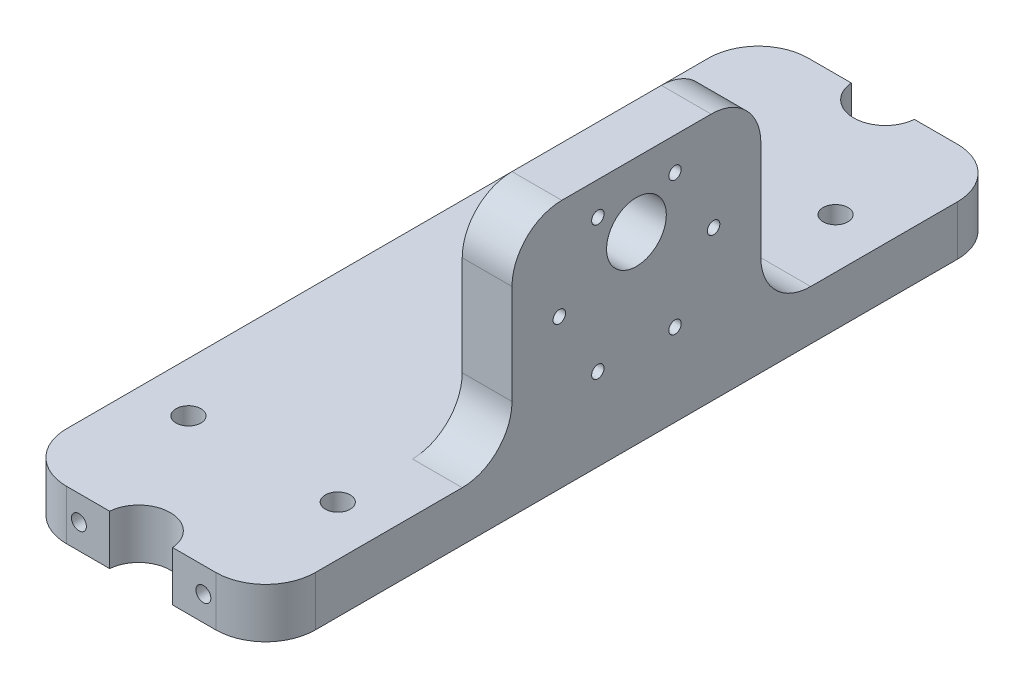
SolidWorks part; units mm, degrees
material "Nylon 101"
ref_plane "Front" through (0, 0, 0) normal (0, 0, 1) x (1, 0, 0)
ref_plane "Top" through (0, 0, 0) normal (0, 1, 0) x (1, 0, 0)
ref_plane "Right" through (0, 0, 0) normal (1, 0, 0) x (0, 0, -1)
sketch "Sketch1" plane through (0, 0, 0) normal (0, 1, 0) x (1, 0, 0)
  line L0 (-25, -75) -> (25, -75) construction
  line L1 (-15, 50) -> (15, 50) construction
  line L2 (0, -75) -> (0, 75) construction
  line L3 (-25, -75) -> (-25, 75)
  line L4 (25, -75) -> (25, 75)
  line L5 (25, 0) -> (0, 0) construction
  line L6 (25, 17) -> (97.2, 17)
  line L7 (25, 17) -> (25, -17)
  line L8 (25, -17) -> (97.2, -17)
  line L9 (97.2, 17) -> (97.2, -17)
  line L10 (-15, 50) -> (-15, -50) construction
  line L11 (-15, -50) -> (15, -50) construction
  line L12 (15, 50) -> (15, -50) construction
  line L13 (-25, -75.5) -> (25, -75.5)
  line L14 (-25, -74.5) -> (25, -74.5)
  line L15 (-25, 75.5) -> (25, 75.5)
  line L16 (-25, 74.5) -> (25, 74.5)
  circle A0 centre (0, 75) radius 6.35
  circle A1 centre (0, -75) radius 6.35
  arc A2 (-25, -75) -> (25, -75) centre (0, -75) ccw
  arc A3 (25, 75) -> (-25, 75) centre (0, 75) ccw
  circle A6 centre (-15, 50) radius 2.5
  circle A7 centre (-15, -50) radius 2.5
  circle A8 centre (15, -50) radius 2.5
  circle A9 centre (15, 50) radius 2.5
  point P8 (0, 0)
  point P24 (0, -50)
  dimension "D2" = 12.7
  dimension "D5" = 25
  dimension "D1" = 5
  dimension "D3" = 150
  dimension "D4" = 25
  dimension "D6" = 25
  dimension "D7" = 34
  dimension "D8" = 72.2
  dimension "D9" = 30
  dimension "D10" = 0.5
  dimension "D11" = 0.5
extrude "Boss-Extrude1" add sketch "Sketch1" along normal blind 10 contours A1 L14 L4 L16 A0 L3 A9 A8 A7 A6 region at (0, 0, 0)
sketch "Sketch2" plane through (0, 0, 0) normal (0, 1, 0) x (1, 0, 0)
  line L0 (25, -75) -> (25, 75) construction
  line L1 (25, 25) -> (15, 25)
  line L2 (25, 25) -> (25, -25)
  line L3 (25, -25) -> (15, -25)
  line L4 (15, 25) -> (15, -25)
  line L6 (25, 0) -> (0, 0) construction
  line L7 (25, 0) -> (0, 0) construction
  dimension "D1" = 50
  dimension "D2" = 10
extrude "Boss-Extrude2" add sketch "Sketch2" along normal blind 50
sketch "Sketch3" plane through (25, 0, 0) normal (1, 0, 0) x (0, 0, -1)
  line L0 (-25, 10) -> (25, 10) construction
  line L1 (0, 10) -> (0, 50) construction
  line L3 (-25, 50) -> (25, 50) construction
  circle A0 centre (0, 30) radius 15.5 construction
  circle A1 centre (0, 30) radius 18.4 construction
  circle A2 centre (-15.5, 30) radius 1.25
  circle A8 centre (0, 37) radius 3 construction
  circle A9 centre (0, 37) radius 6
  circle A10 centre (-7.75, 43.4234) radius 1.25
  circle A11 centre (7.75, 43.4234) radius 1.25
  circle A12 centre (15.5, 30) radius 1.25
  circle A13 centre (7.75, 16.5766) radius 1.25
  circle A14 centre (-7.75, 16.5766) radius 1.25
  dimension "D1" = 31
  dimension "D2" = 2.5
  dimension "D3" = 36.8
  dimension "D4" = 12
  dimension "D6" = 6
  dimension "D7" = 6
  dimension "D5" = 7
extrude "Cut-Extrude1" cut sketch "Sketch3" against normal blind 25
fillet "Fillet1" radius 10 8 edges at (-25, 5, -74.5) (25, 5, -74.5) (-25, 5, 74.5) (25, 5, 74.5) (20, 10, -25) (20, 50, -25) (20, 50, 25) (20, 10, 25)
sketch "Sketch4" plane through (0, 0, 74.5) normal (0, 0, 1) x (1, 0, 0)
  line L0 (-12.5, 0) -> (-12.5, 10) construction
  line L1 (-15, 0) -> (-6.3303, 0) construction
  line L2 (12.5, 10) -> (12.5, 0) construction
  line L3 (6.3303, 0) -> (15, 0) construction
  line L8 (-15, 10) -> (-6.3303, 10) construction
  line L9 (6.3303, 10) -> (15, 10) construction
  circle A0 centre (-12.5, 5) radius 1.5
  circle A1 centre (12.5, 5) radius 1.5
  dimension "D1" = 3
  dimension "D2" = 12.5
  dimension "D3" = 12.5
extrude "Cut-Extrude2" cut sketch "Sketch4" against normal blind 5
extrude "Cut-Extrude3" cut sketch "Sketch4<2>" along normal blind 5 from surface starting at face at (10.6651, 5, -74.5)
sketch "Sketch4<2>" plane through (0, 0, 74.5) normal (0, 0, 1) x (1, 0, 0) same geometry as "Sketch4"
